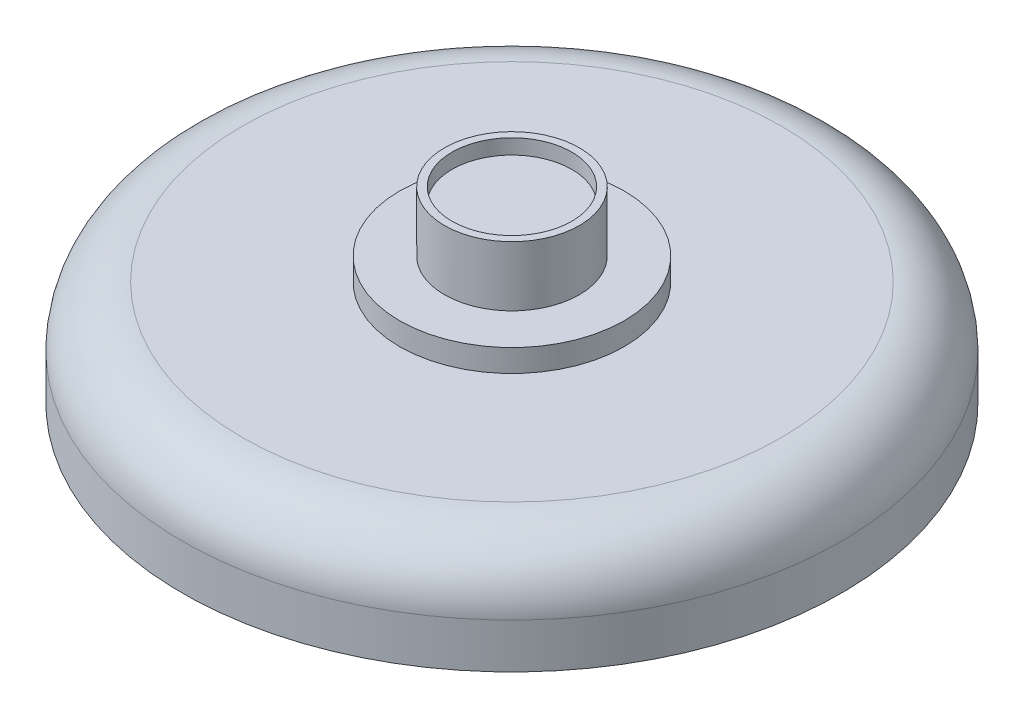
SolidWorks part; units mm, degrees
ref_plane "Front Plane" through (0, 0, 0) normal (0, 0, 1) x (1, 0, 0)
ref_plane "Top Plane" through (0, 0, 0) normal (0, 1, 0) x (1, 0, 0)
ref_plane "Right Plane" through (0, 0, 0) normal (1, 0, 0) x (0, 0, -1)
sketch "Sketch1" plane through (0, 0, 0) normal (0, 1, 0) x (1, 0, 0)
  line L1 (-20.5, -35) -> (20.5, -35)
  line L2 (-25.5, -30) -> (-25.5, 30)
  line L3 (-20.5, 35) -> (20.5, 35)
  line L4 (25.5, -30) -> (25.5, 30)
  line L5 (-25.5, -35) -> (25.5, 35) construction
  line L6 (-25.5, 35) -> (25.5, -35) construction
  arc A0 (-20.5, -35) -> (-25.5, -30) centre (-20.5, -30) cw
  arc A1 (20.5, -35) -> (25.5, -30) centre (20.5, -30) ccw
  arc A2 (20.5, 35) -> (25.5, 30) centre (20.5, 30) cw
  arc A3 (-25.5, 30) -> (-20.5, 35) centre (-20.5, 30) cw
  point P0 (0, 0)
  dimension "D3" = 5
  dimension "D1" = 51
  dimension "D2" = 70
extrude "Boss-Extrude1" add sketch "Sketch1" along normal blind 1.5
sketch "Sketch2" plane through (0, 1.5, 0) normal (0, 1, 0) x (1, 0, 0)
  line L0 (-17.5, 24.5) -> (-17.5, 28.5) construction
  line L1 (-17.5, -26.5) -> (17.5, -26.5) construction
  line L2 (-17.5, -26.5) -> (-17.5, 26.5) construction
  line L3 (-17.5, 26.5) -> (17.5, 26.5) construction
  line L4 (17.5, -26.5) -> (17.5, 26.5) construction
  line L5 (-17.5, -26.5) -> (17.5, 26.5) construction
  line L6 (-17.5, 26.5) -> (17.5, -26.5) construction
  line L7 (-21.5, 24.5) -> (-21.5, 28.5)
  line L8 (-13.5, 24.5) -> (-13.5, 28.5)
  line L9 (17.5, 24.5) -> (17.5, 28.5) construction
  line L10 (13.5, 24.5) -> (13.5, 28.5)
  line L11 (21.5, 24.5) -> (21.5, 28.5)
  arc A0 (-21.5, 24.5) -> (-13.5, 24.5) centre (-17.5, 24.5) ccw
  arc A1 (-13.5, 28.5) -> (-21.5, 28.5) centre (-17.5, 28.5) ccw
  arc A2 (13.5, 24.5) -> (21.5, 24.5) centre (17.5, 24.5) ccw
  arc A3 (21.5, 28.5) -> (13.5, 28.5) centre (17.5, 28.5) ccw
  point P0 (0, 0)
  point P8 (-17.5, 26.5)
  point P14 (17.5, 26.5)
  dimension "D3" = 4
  dimension "D5" = 4
  dimension "D6" = 4
  dimension "D1" = 35
  dimension "D2" = 53
  dimension "D4" = 4
extrude "Cut-Extrude1" cut sketch "Sketch2" against normal blind 2
mirror "Mirror1" about plane through (0, 0, 0) normal (0, 0, 1) of "Cut-Extrude1"
sketch "Sketch3" plane through (0, 1.5, 0) normal (0, 1, 0) x (1, 0, 0)
  circle A0 centre (0, 0) radius 4
  dimension "D1" = 8
extrude "Cut-Extrude2" cut sketch "Sketch3" against normal blind 2
sketch "Sketch4" plane through (0, 1.5, 0) normal (0, 1, 0) x (1, 0, 0)
  circle A0 centre (0, 0) radius 20
  dimension "D1" = 40
extrude "Cut-Extrude3" cut sketch "Sketch4" against normal blind 0.5
fillet "Fillet1" radius 1 1 edges at (0, 1.5, 20)
sketch "Sketch5" plane through (0, 0, 0) normal (0, -1, 0) x (1, 0, 0)
  circle A0 centre (0, 0) radius 22
  dimension "D1" = 44
extrude "Boss-Extrude2" add sketch "Sketch5" along normal blind 3
sketch "Sketch6" plane through (0, 1, 0) normal (0, 1, 0) x (1, 0, 0)
  circle A0 centre (0, 0) radius 6.5
  dimension "D1" = 13
extrude "Boss-Extrude3" [suppressed] add sketch "Sketch6" along normal blind 2
chamfer "Chamfer1" [suppressed] distance 0.5 angle 30
sketch "Sketch7" plane through (0, -3, 0) normal (0, -1, 0) x (1, 0, 0)
  circle A0 centre (0, 0) radius 7.5
  dimension "D1" = 15
extrude "Boss-Extrude4" add sketch "Sketch7" along normal blind 1.5
sketch "Sketch8" plane through (0, -4.5, 0) normal (0, -1, 0) x (1, 0, 0)
  circle A0 centre (0, 0) radius 22
extrude "Boss-Extrude5" add sketch "Sketch8" along normal blind 7
sketch "Sketch9" plane through (0, 1, 0) normal (0, 1, 0) x (1, 0, 0)
  circle A0 centre (0, 0) radius 6.5
  circle A1 centre (0, 0) radius 8
  dimension "D1" = 16
extrude "Cut-Extrude4" cut sketch "Sketch9" against normal blind 3
fillet "Fillet4" radius 3 1 edges at (0, 1, 8)
sketch "Sketch10" plane through (0, 1.5, 0) normal (0, 1, 0) x (1, 0, 0)
  circle A0 centre (0, 0) radius 20.866
  circle A1 centre (0, 0) radius 46.1444
extrude "Cut-Extrude5" cut sketch "Sketch10" against normal up to surface (6 mm away) up to face at (0, -4.5, -22)
sketch "Sketch11" plane through (0, -3, 0) normal (0, -1, 0) x (1, 0, 0)
  circle A1 centre (0, 0) radius 20.866
  circle A2 centre (0, 0) radius 20.866
  circle A3 centre (0, 0) radius 23.866
  circle A4 centre (0, 0) radius 23.866
  dimension "D1" = 0
  dimension "D2" = 3
extrude "Boss-Extrude6" [suppressed] add sketch "Sketch11" against normal blind 4.5
sketch "Sketch12" plane through (0, -3, 0) normal (0, -1, 0) x (1, 0, 0)
  circle A0 centre (0, 0) radius 6.5
  circle A1 centre (0, 0) radius 20.866
  circle A2 centre (0, 0) radius 20.866
  dimension "D1" = 0
extrude "Cut-Extrude6" cut sketch "Sketch12" against normal blind 10
fillet "Fillet5" radius 4 1 edges at (0, -4.5, -22)
sketch "Sketch13" plane through (0, 1, 0) normal (0, 1, 0) x (1, 0, 0)
  circle A0 centre (0, 0) radius 4.5
  circle A1 centre (0, 0) radius 8.8966
  dimension "D1" = 9
extrude "Cut-Extrude7" cut sketch "Sketch13" against normal up to surface (4 mm away) up to face at (0, -3, -6.5)
sketch "Sketch14" plane through (0, 0, 0) normal (0, 1, 0) x (1, 0, 0)
  circle A1 centre (0, 0) radius 4
  circle A2 centre (0, 0) radius 4
  dimension "D1" = 0
extrude "Boss-Extrude7" add sketch "Sketch14" against normal blind 18
